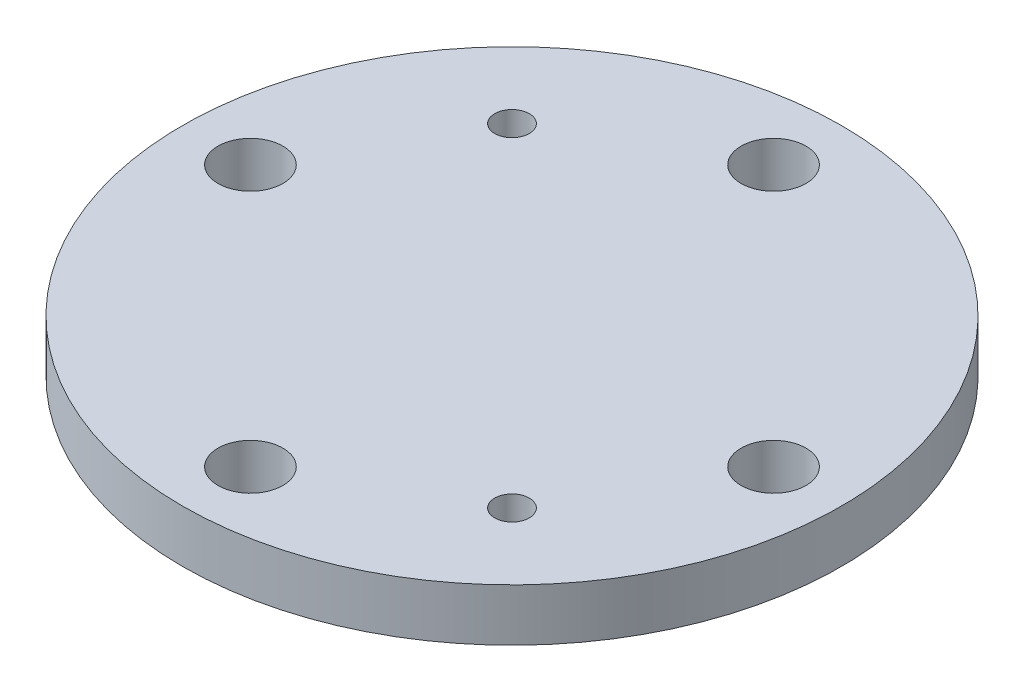
SolidWorks part; units mm, degrees
ref_plane "Front Plane" through (0, 0, 0) normal (0, 0, 1) x (1, 0, 0)
ref_plane "Top Plane" through (0, 0, 0) normal (0, 1, 0) x (1, 0, 0)
ref_plane "Right Plane" through (0, 0, 0) normal (1, 0, 0) x (0, 0, -1)
sketch "Sketch1" plane through (0, 0, 0) normal (0, 1, 0) x (1, 0, 0)
  line L0 (-15.9099, 15.9099) -> (0, 0) construction
  line L1 (0, 0) -> (15.9099, -15.9099) construction
  line L3 (0, -55) -> (0, 55) construction
  circle A0 centre (0, 0) radius 31.5
  circle A1 centre (0, 0) radius 25 construction
  circle A2 centre (0, 25) radius 3.1
  circle A3 centre (25, 0) radius 3.1
  circle A4 centre (0, -25) radius 3.1
  circle A5 centre (-25, 0) radius 3.1
  circle A6 centre (-15.9099, 15.9099) radius 1.65
  circle A7 centre (15.9099, -15.9099) radius 1.65
  circle A8 centre (0, 0) radius 22.5 construction
  point P8 (0, 0)
  point P15 (0, 0)
  point P18 (0, 0)
  dimension "D1" = 63
  dimension "D2" = 50
  dimension "D3" = 6.2
  dimension "D4" = 4
  dimension "D5" = 45
  dimension "D6" = 3.3
  dimension "D7" = 45
extrude "Boss-Extrude1" add sketch "Sketch1" along normal blind 5 contours A0 | A5 | A2 | A3 | A4 | A6 | A7
ref_axis "Axis1" through (-15.9099, 5, -15.9099) along (0, -1, 0)
ref_axis "Axis2" through (15.9099, 5, 15.9099) along (0, -1, 0)
equation "\"1。5\"=2.53495"
